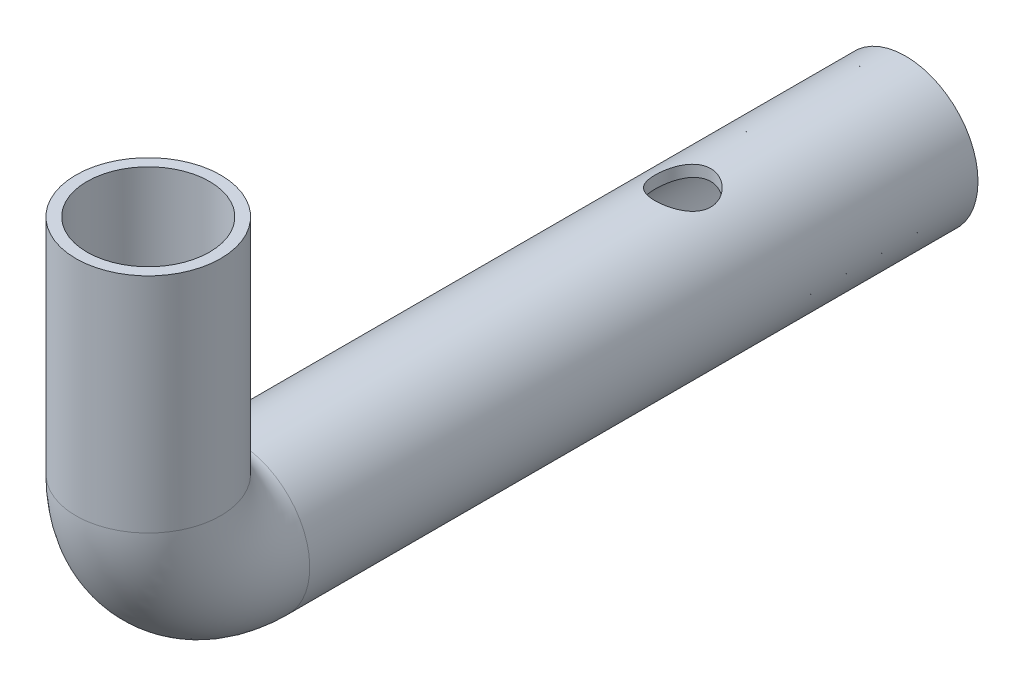
SolidWorks part; units mm, degrees
ref_plane "Front Plane" through (0, 0, 0) normal (0, 0, 1) x (1, 0, 0)
ref_plane "Top Plane" through (0, 0, 0) normal (0, 1, 0) x (1, 0, 0)
ref_plane "Right Plane" through (0, 0, 0) normal (1, 0, 0) x (0, 0, -1)
sketch "Sketch2" plane through (0, 0, 0) normal (1, 0, 0) x (0, 0, -1)
  line L0 (0, 0) -> (-60, 0)
  line L1 (-68, 8) -> (-68, 28)
  arc A1 (-60, 0) -> (-68, 8) centre (-60, 8) cw
  point P4 (0, 0)
  point P6 (0, 0)
  point P8 (0, 0)
  point P9 (0, 0)
  point P10 (0, 0)
  point P12 (0, 0)
  point P13 (0, 0)
  point P14 (0, 0)
  point P15 (0, 0)
  dimension "D1" = 8
  dimension "D2" = 60
  dimension "D3" = 20
sweep "Sweep5" add path "Sketch2" circular profile diameter 13 parameters "D3"=13
sweep "Cut-Sweep1" cut path "Sketch2<2>" circular profile diameter 11 parameters "D3"=11
sketch "Sketch2<2>" plane through (0, 0, 0) normal (1, 0, 0) x (0, 0, -1) same geometry as "Sketch2"
sketch "Sketch30" plane through (0, 0, 0) normal (0, 1, 0) x (1, 0, 0)
  line L0 (6.5, 0) -> (-6.5, 0) construction
  circle A0 centre (0, -20) radius 2.5
  point P4 (0, 0)
  point P6 (-5.6773, -0.621)
  dimension "D1" = 5
  dimension "D2" = 20
extrude "Cut-Extrude1" cut sketch "Sketch30" along normal through all both and the other way through all contours A0
